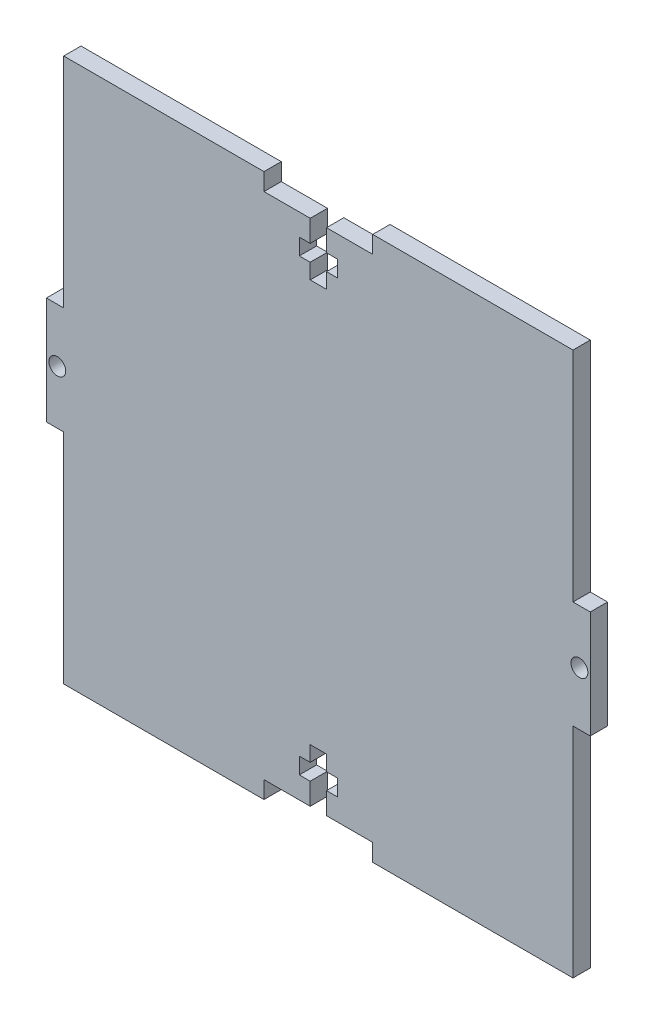
SolidWorks part; units mm, degrees
ref_plane "Front Plane" through (0, 0, 0) normal (0, 0, 1) x (1, 0, 0)
ref_plane "Top Plane" through (0, 0, 0) normal (0, 1, 0) x (1, 0, 0)
ref_plane "Right Plane" through (0, 0, 0) normal (1, 0, 0) x (0, 0, -1)
sketch "Sketch1" plane through (0, 0, 0) normal (0, 0, 1) x (1, 0, 0)
  line L0 (0, 40) -> (0, -40) construction
  line L5 (-50, -50) -> (50, 50) construction
  line L6 (-50, 50) -> (50, -50) construction
  line L7 (-100, 0) -> (100, 0) construction
  line L32 (-50, 50) -> (50, 50)
  line L35 (50, 50) -> (50, -50)
  line L36 (50, -50) -> (-50, -50)
  line L37 (-50, -50) -> (-50, 50)
  point P0 (0, 0)
  dimension "D1" = 100
  dimension "D2" = 100
extrude "Boss-Extrude2" add sketch "Sketch1" along normal blind 3.18
sketch "Sketch2" plane through (0, 0, 3.18) normal (0, 0, 1) x (1, 0, 0)
  line L0 (0, -50) -> (0, 50) construction
  line L1 (-123.0225, 0) -> (147.0753, 0) construction
  line L2 (50, 50) -> (-50, 50) construction
  line L4 (-10, 50) -> (-10, 46.82)
  line L5 (-10, 46.82) -> (-1.5, 46.82)
  line L6 (10, 50) -> (10, 46.82)
  line L7 (1.5, 46.82) -> (10, 46.82)
  line L9 (-1.5, 46.82) -> (-1.5, 42.82)
  line L10 (-1.5, 37) -> (1.5, 37)
  line L11 (1.5, 46.82) -> (1.5, 42.82)
  line L12 (-3.5, 42.82) -> (-1.5, 42.82)
  line L13 (-3.5, 42.82) -> (-3.5, 39.82)
  line L14 (-3.5, 39.82) -> (-1.5, 39.82)
  line L15 (3.5, 42.82) -> (3.5, 39.82)
  line L16 (1.5, 42.82) -> (3.5, 42.82)
  line L17 (-1.5, 39.82) -> (-1.5, 37)
  line L18 (1.5, 39.82) -> (1.5, 37)
  line L19 (1.5, 39.82) -> (3.5, 39.82)
  line L20 (-10, 50) -> (10, 50)
  line L21 (-50, -50) -> (50, -50) construction
  line L22 (-50, 50) -> (-50, -50) construction
  line L23 (-50, 9.875) -> (-46.82, 9.875)
  line L24 (-50, 9.875) -> (-50, 50)
  line L25 (-50, 50) -> (-46.82, 50)
  line L26 (-46.82, 9.875) -> (-46.82, 50)
  line L28 (-50, -9.875) -> (-46.82, -9.875)
  line L29 (-50, -9.875) -> (-50, -50)
  line L30 (-50, -50) -> (-46.82, -50)
  line L31 (-46.82, -9.875) -> (-46.82, -50)
  circle A0 centre (-48, 0) radius 1.55
  dimension "D11" = 3.1
  dimension "D12" = 2
  dimension "D1" = 4
  dimension "D2" = 3
  dimension "D3" = 3
  dimension "D4" = 20
  dimension "D5" = 7
  dimension "D6" = 3.18
  dimension "D7" = 13
  dimension "D8" = 19.75
  dimension "D9" = 3.18
  dimension "D10" = 3.18
extrude "Cut-Extrude1" cut sketch "Sketch2" against normal through all
mirror "Mirror1" about plane through (0, 0, 0) normal (0, 1, 0) of "Cut-Extrude1"
mirror "Mirror3" about plane through (0, 0, 0) normal (1, 0, 0) of "Cut-Extrude1"
